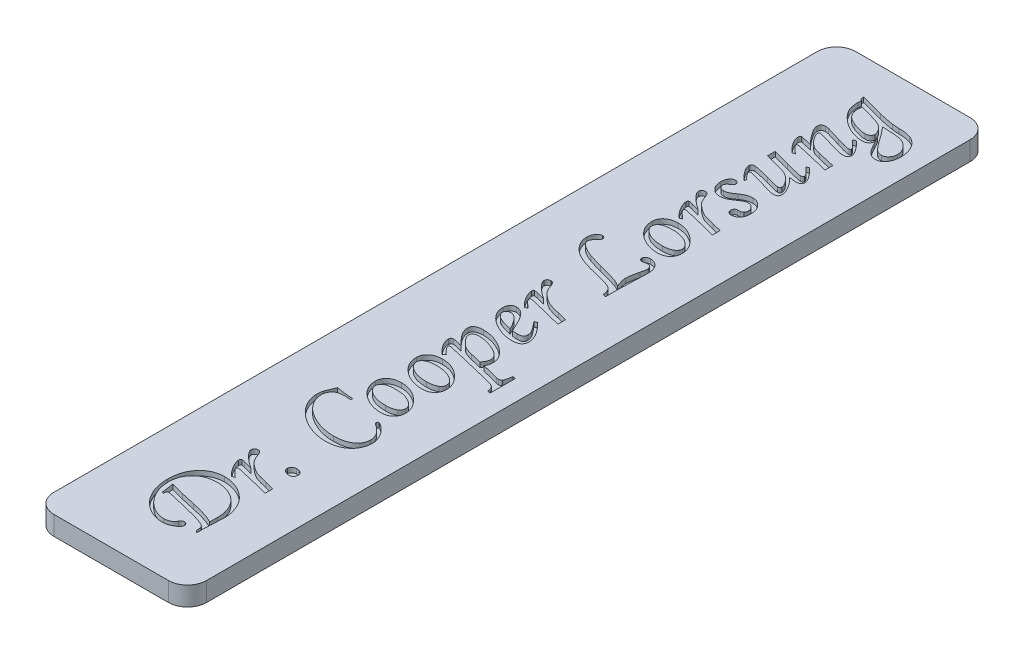
SolidWorks part; units mm, degrees
ref_plane "Front Plane" through (0, 0, 0) normal (0, 0, 1) x (1, 0, 0)
ref_plane "Top Plane" through (0, 0, 0) normal (0, 1, 0) x (1, 0, 0)
ref_plane "Right Plane" through (0, 0, 0) normal (1, 0, 0) x (0, 0, -1)
sketch "Sketch1" plane through (0, 0, 0) normal (0, 0, 1) x (1, 0, 0)
  line L0 (0, 1.5875) -> (0, -1.5875)
  line L1 (-12.7, 0) -> (12.7, 0) construction
  point P6 (0, 0)
  dimension "Width" = 25.4
  dimension "Thk" = 3.175
sketch "Sketch2" plane through (0, 0, 0) normal (1, 0, 0) x (0, 0, -1)
  line L0 (66.675, 0) -> (-66.675, 0)
  point P4 (0, 0)
  dimension "Length" = 133.35
sketch "Sketch3" plane through (0, 0, 0) normal (0, 0, 1) x (1, 0, 0)
  line L1 (12.7, 1.5875) -> (-12.7, 1.5875)
  line L2 (12.7, 1.5875) -> (12.7, -1.5875)
  line L3 (12.7, -1.5875) -> (-12.7, -1.5875)
  line L4 (-12.7, 1.5875) -> (-12.7, -1.5875)
  line L5 (12.7, 1.5875) -> (-12.7, -1.5875) construction
  line L6 (12.7, -1.5875) -> (-12.7, 1.5875) construction
  point P0 (0, 0)
extrude "Boss-Extrude1" add sketch "Sketch3" along normal up to vertex (66.675 mm away) and the other way up to vertex (66.675 mm away) up to point (0, 0, 66.675) other way up to point (0, 0, -66.675)
sketch "Sketch5" plane through (0, 1.5875, 0) normal (0, 1, 0) x (1, 0, 0)
  line L0 (-9.525, 66.675) -> (9.525, 66.675)
  line L1 (12.7, 63.5) -> (12.7, -63.5)
  line L2 (9.525, -66.675) -> (-9.525, -66.675)
  line L3 (-12.7, -63.5) -> (-12.7, 63.5)
  arc A0 (9.525, -66.675) -> (12.7, -63.5) centre (9.525, -63.5) ccw construction
  arc A1 (9.525, -66.675) -> (12.7, -63.5) centre (9.525, -63.5) ccw
  arc A2 (-12.7, -63.5) -> (-9.525, -66.675) centre (-9.525, -63.5) ccw construction
  arc A3 (-12.7, -63.5) -> (-9.525, -66.675) centre (-9.525, -63.5) ccw
  arc A4 (12.7, 63.5) -> (9.525, 66.675) centre (9.525, 63.5) ccw construction
  arc A5 (12.7, 63.5) -> (9.525, 66.675) centre (9.525, 63.5) ccw
  arc A6 (-9.525, 66.675) -> (-12.7, 63.5) centre (-9.525, 63.5) ccw construction
  arc A7 (-9.525, 66.675) -> (-12.7, 63.5) centre (-9.525, 63.5) ccw
extrude "Cut-Extrude2" cut sketch "Sketch5" against normal through all flip side to cut
sketch "Sketch4" plane through (0, 1.5875, 0) normal (0, 1, 0) x (1, 0, 0)
  line L0 (0, 0) -> (5, 0) construction
  line L1 (5, -66.675) -> (5, 66.675) construction
  line L2 (9.525, 66.675) -> (-9.525, 66.675) construction
  text T0 "Dr. Cooper Lorsung" font "Monotype Corsiva" height 10
  point P8 (5, 0)
  dimension "D1" = 5
extrude "Cut-Extrude1" cut sketch "Sketch4" against normal blind 0.7937
